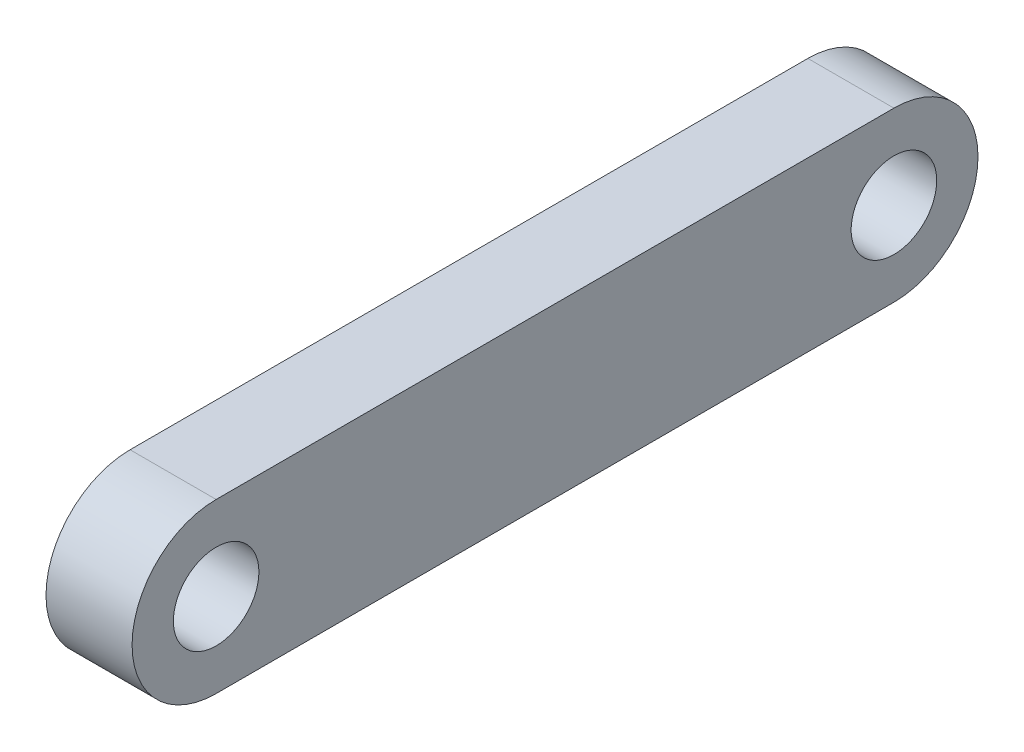
SolidWorks part; units mm, degrees
material "6061-T6 (SS)"
ref_plane "Front Plane" through (0, 0, 0) normal (0, 0, 1) x (1, 0, 0)
ref_plane "Top Plane" through (0, 0, 0) normal (0, 1, 0) x (1, 0, 0)
ref_plane "Right Plane" through (0, 0, 0) normal (1, 0, 0) x (0, 0, -1)
sketch "Sketch1" plane through (0, 0, 0) normal (1, 0, 0) x (0, 0, -1)
  line L0 (0, 0) -> (32, 0) construction
  line L1 (0, 3.9688) -> (32, 3.9688)
  line L2 (0, -3.9688) -> (32, -3.9688)
  arc A0 (0, 3.9688) -> (0, -3.9688) centre (0, 0) ccw
  arc A1 (32, -3.9688) -> (32, 3.9688) centre (32, 0) ccw
  circle A2 centre (0, 0) radius 2.0193
  circle A3 centre (32, 0) radius 2.0193
  point P3 (16, 0)
  dimension "D1" = 3.9688
  dimension "D3" = 4.0386
  dimension "D2" = 32
extrude "Boss-Extrude1" add sketch "Sketch1" along normal blind 4.064
